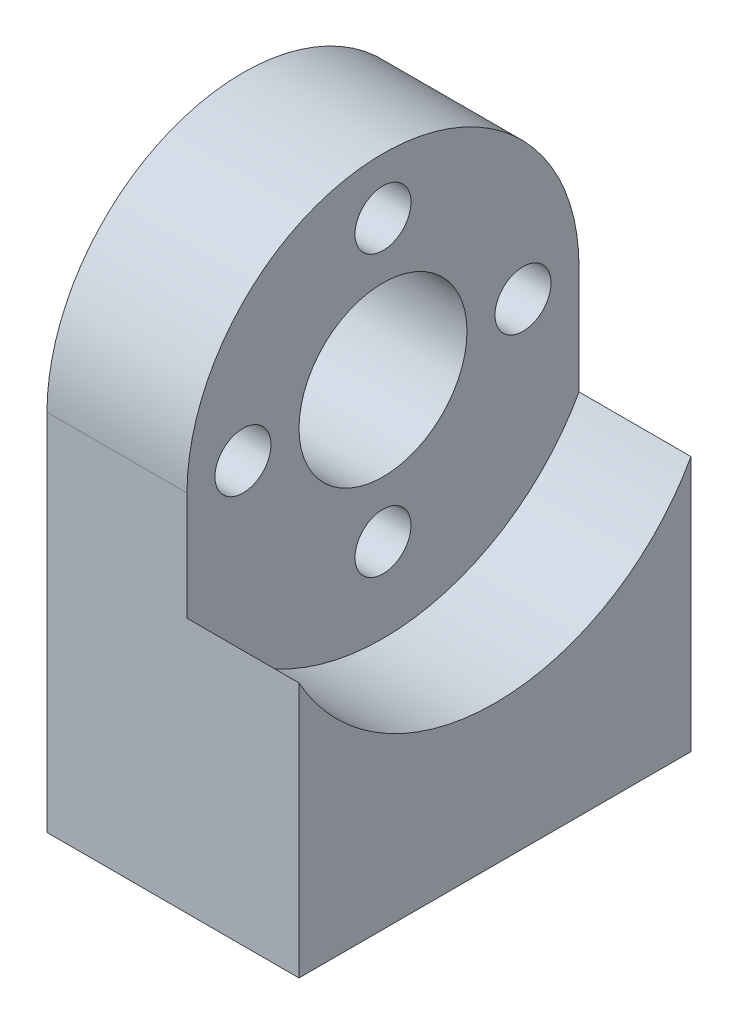
SolidWorks part; units mm, degrees
ref_plane "Front Plane" through (0, 0, 0) normal (0, 0, 1) x (1, 0, 0)
ref_plane "Top Plane" through (0, 0, 0) normal (0, 1, 0) x (1, 0, 0)
ref_plane "Right Plane" through (0, 0, 0) normal (1, 0, 0) x (0, 0, -1)
sketch "Sketch1" plane through (0, 0, 0) normal (1, 0, 0) x (0, 0, -1)
  line L0 (0, 13) -> (0, 0)
  line L1 (0, 0) -> (14, 0)
  line L2 (14, 0) -> (14, 13)
  arc A0 (0, 13) -> (14, 13) centre (7, 13) cw
  circle A1 centre (7, 13) radius 3
  circle A2 centre (12, 13) radius 1
  dimension "D2" = 6
  dimension "D4" = 2
  dimension "D1" = 14
  dimension "D3" = 5
  dimension "D5" = 13
extrude "Boss-Extrude1" add sketch "Sketch1" along normal blind 9
sketch "Sketch2" plane through (9, 0, 0) normal (1, 0, 0) x (0, 0, -1)
  circle A0 centre (7, 13) radius 8
  dimension "D1" = 16
extrude "Cut-Extrude1" cut sketch "Sketch2" against normal blind 4
pattern_circular "CirPattern1" count 4 over 360 about axis through (5, 13, -7) along (1, 0, 0) of face at (0, 13, -13)
hole_wizard "Tap Drill for M3x0.5 Tap1" positions "Sketch4" profile "Sketch3" hole size "M3x0.5" standard "ANSI Metric"
sketch "Sketch4" plane through (0, 0, 0) normal (0, -1, 0) x (-1, 0, 0)
  line L0 (-9, 0) -> (-9, 14) construction
  line L2 (-9, 0) -> (0, 0) construction
  line L3 (-9, 14) -> (0, 14) construction
  point P0 (-3, 11)
  point P2 (-7, 3)
  dimension "D1" = 2
  dimension "D2" = 6
  dimension "D3" = 3
  dimension "D4" = 3
sketch "Sketch3" plane through (3, 0, -11) normal (1, 0, 0) x (0, 0, -1)
  line L0 (0, 0) -> (0, 4.7511)
  line L1 (0, 4.7511) -> (1.25, 4)
  line L2 (1.25, 4) -> (1.25, 0)
  line L5 (1.25, 0) -> (0, 0)
  line L10 (0, 4.7511) -> (-1.25, 4) construction
  line L11 (0, -6.35) -> (0, 107.95) construction
  dimension "Hole Dia." = 2.5
  dimension "Hole Depth" = 4
  dimension "Drill Angle" = 118
sketch "Sketch5" plane through (0, 0, 0) normal (0, -1, 0) x (1, 0, 0)
  line L1 (7, -11) -> (3, -11) construction
  line L2 (7, -11) -> (7, -3) construction
  line L3 (7, -3) -> (3, -3) construction
  line L4 (3, -11) -> (3, -3) construction
  circle A0 centre (3, -3) radius 1
  circle A1 centre (7, -11) radius 1
  dimension "D1" = 2
extrude "Cut-Extrude2" cut sketch "Sketch5" against normal blind 4
chamfer "Chamfer1" distance 1 angle 45 4 edges at (0, 7, -7) (0, 13, -13) (0, 13, -1) (0, 19, -7)
